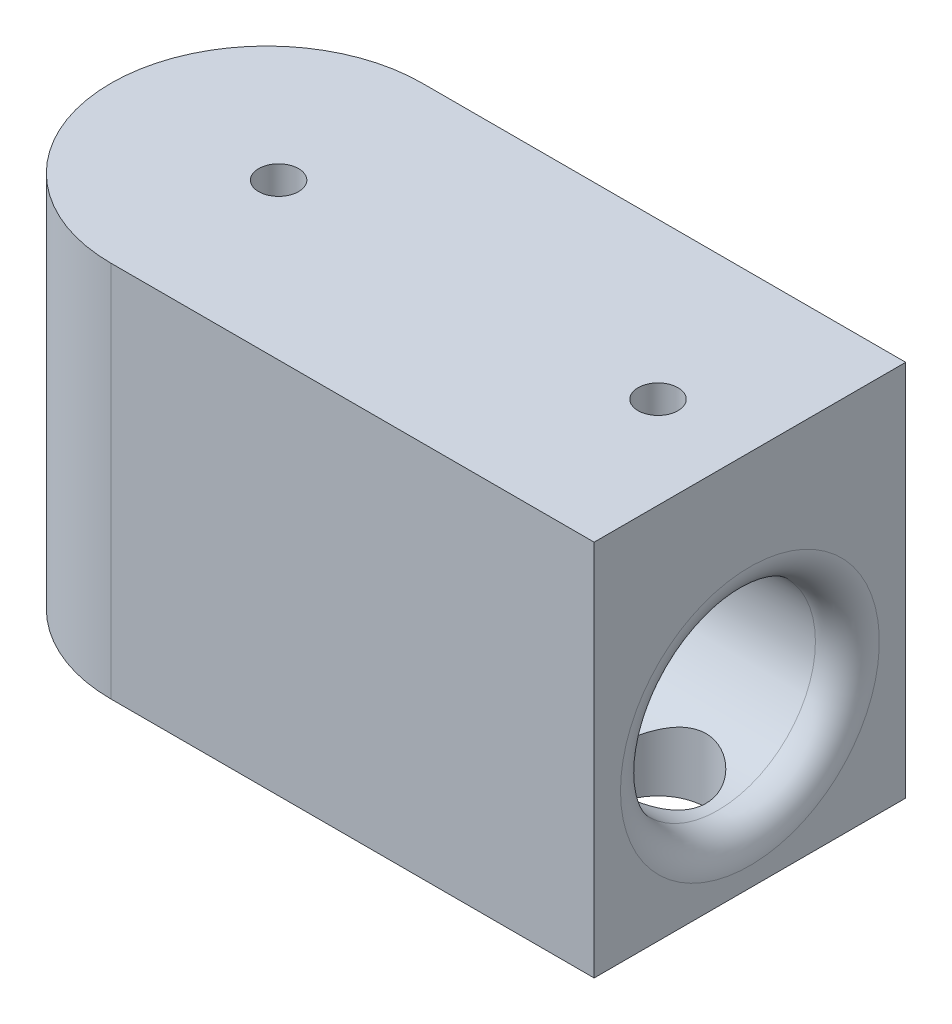
SolidWorks part; units mm, degrees
ref_plane "Front Plane" through (0, 0, 0) normal (0, 0, 1) x (1, 0, 0)
ref_plane "Top Plane" through (0, 0, 0) normal (0, 1, 0) x (1, 0, 0)
ref_plane "Right Plane" through (0, 0, 0) normal (1, 0, 0) x (0, 0, -1)
sketch "Sketch1" plane through (0, 0, 0) normal (0, 1, 0) x (1, 0, 0)
  line L1 (0, 0) -> (40, 0)
  line L2 (0, 0) -> (0, 19.5)
  line L3 (0, 19.5) -> (40, 19.5)
  line L4 (40, 0) -> (40, 19.5)
  dimension "D1" = 19.5
  dimension "D2" = 40
extrude "Boss-Extrude1" add sketch "Sketch1" along normal blind 23.625
sketch "Sketch2" plane through (40, 0, 0) normal (1, 0, 0) x (0, 0, -1)
  line L0 (9.75, 23.625) -> (9.75, 9.3125)
  line L1 (0, 23.625) -> (19.5, 23.625) construction
  circle A0 centre (9.75, 9.3125) radius 6.1
  dimension "D2" = 12.2
  dimension "D1" = 14.3125
extrude "Cut-Extrude1" cut sketch "Sketch2" against normal blind 36.25 contours A0 region at (40, 5.1211, -5.5586)
sketch "Sketch3" plane through (3.75, 0, 0) normal (1, 0, 0) x (0, 0, -1)
  circle A0 centre (9.75, 9.3125) radius 5
extrude "Cut-Extrude2" cut sketch "Sketch3" against normal up to next
sketch "Sketch5" plane through (0, 0, 0) normal (0, -1, 0) x (1, 0, 0)
  line L0 (40, -9.75) -> (34.25, -9.75)
  line L1 (40, 0) -> (40, -19.5) construction
  line L2 (34.25, -9.75) -> (10.5, -9.75)
  circle A0 centre (34.25, -9.75) radius 3
  circle A1 centre (10.5, -9.75) radius 3
  dimension "D3" = 6
  dimension "D4" = 6
  dimension "D1" = 5.75
  dimension "D2" = 23.75
extrude "Cut-Extrude3" cut sketch "Sketch5" against normal blind 18 contours A1 | L2 A0 L0 | L0 A0 L2 region at (34.25, 0, -11.0232) region at (34.25, 0, -8.4768) region at (7.5849, 0, -9.75)
sketch "Sketch6" plane through (0, 18, 0) normal (0, -1, 0) x (1, 0, 0)
  circle A0 centre (10.5, -9.75) radius 1.25
  circle A1 centre (34.25, -9.75) radius 1.25
extrude "Cut-Extrude4" cut sketch "Sketch6" against normal up to next
sketch "Sketch7" plane through (0, 0, 0) normal (0, -1, 0) x (1, 0, 0)
  line L0 (34.25, -9.75) -> (34.25, -3)
  line L1 (34.25, -3) -> (20, -3)
  line L2 (34.25, -9.75) -> (10.5, -9.75)
  circle A0 centre (20, -3) radius 1.25
  circle A1 centre (20, -16.5) radius 1.25
  dimension "D1" = 6.75
  dimension "D2" = 14.25
extrude "Cut-Extrude5" cut sketch "Sketch7" against normal blind 6.75 contours A0 | A1 region at (18.7854, 0, -3) region at (20, 0, -16.5)
fillet "Fillet1" radius 2 1 edges at (40, 9.3125, -15.85)
fillet "Fillet2" radius 9.75 2 edges at (0, 11.8125, 0) (0, 11.8125, -19.5)
